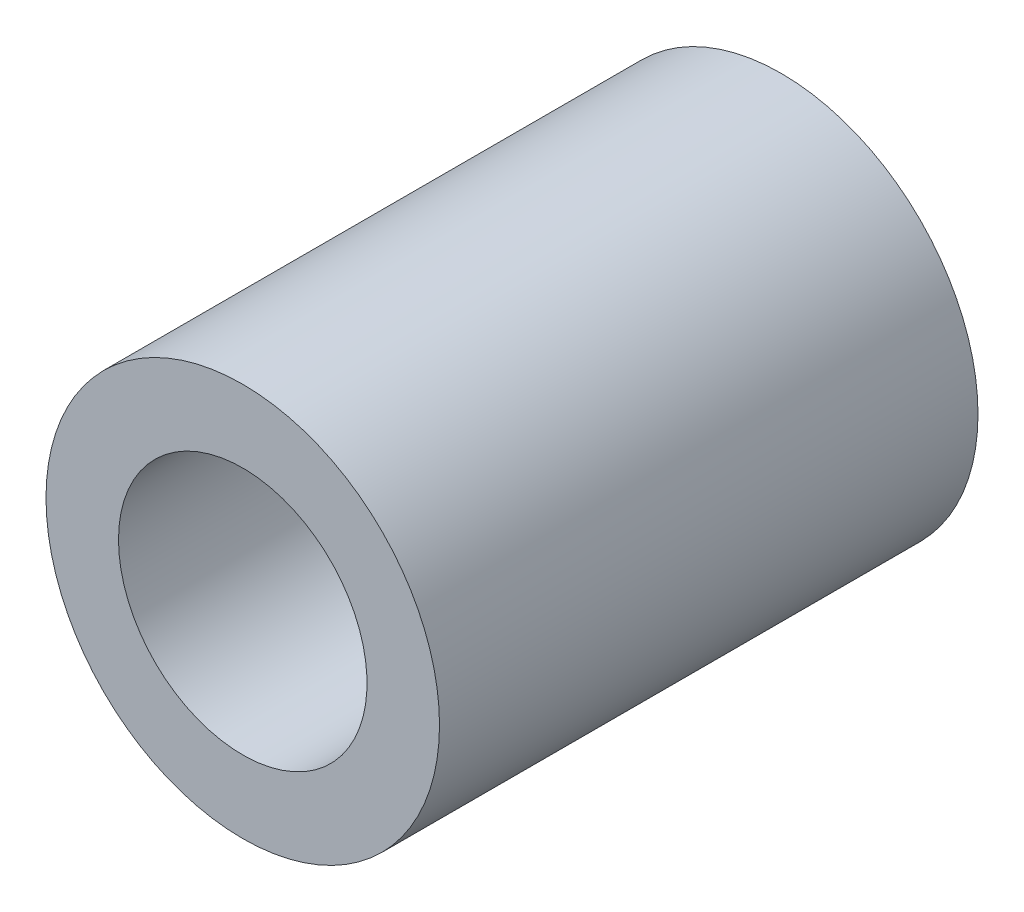
SolidWorks part; units mm, degrees
ref_plane "Alzado" through (0, 0, 0) normal (0, 0, 1) x (1, 0, 0)
ref_plane "Planta" through (0, 0, 0) normal (0, 1, 0) x (1, 0, 0)
ref_plane "Vista lateral" through (0, 0, 0) normal (1, 0, 0) x (0, 0, -1)
sketch "Croquis1" plane through (0, 0, 0) normal (0, 0, 1) x (1, 0, 0)
  circle A0 centre (0, 0) radius 4.75
  circle A1 centre (0, 0) radius 3
  dimension "D1" = 9.5
  dimension "D2" = 6
extrude "Saliente-Extruir1" add sketch "Croquis1" along normal blind 13
